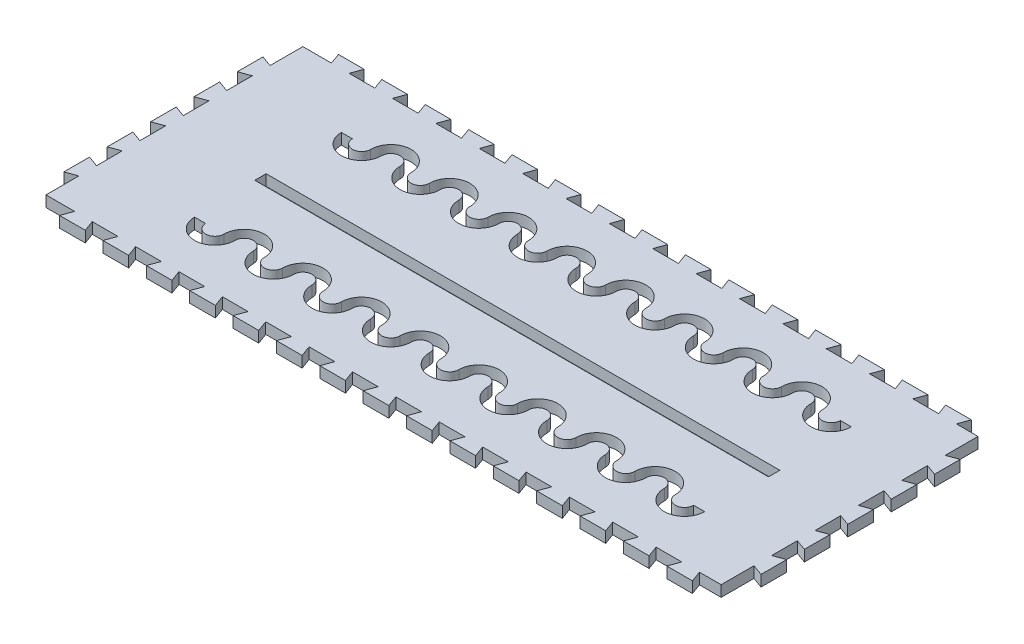
SolidWorks part; units mm, degrees
note: The reader was unsure of these and kept them because the rebuilt part matched: shared geometry of "Sketch1<3>", "Sketch1<4>", "Sketch1<5>".
ref_plane "Front Plane" through (0, 0, 0) normal (0, 0, 1) x (1, 0, 0)
ref_plane "Top Plane" through (0, 0, 0) normal (0, 1, 0) x (1, 0, 0)
ref_plane "Right Plane" through (0, 0, 0) normal (1, 0, 0) x (0, 0, -1)
sketch "Sketch1" plane through (0, 0, 0) normal (0, 1, 0) x (1, 0, 0)
  line L1 (0, 0) -> (184, 0)
  line L2 (0, 0) -> (0, 70)
  line L3 (0, 70) -> (184, 70)
  line L4 (184, 0) -> (184, 70)
  line L5 (165, 31.9) -> (25, 31.9)
  line L6 (165, 31.9) -> (165, 35)
  line L7 (165, 35) -> (25, 35)
  line L8 (25, 31.9) -> (25, 35)
  line L17 (178.0881, 70) -> (179.18, 73)
  line L18 (172.18, 73) -> (173.2719, 70)
  line L19 (178.0881, 70) -> (173.2719, 70)
  line L21 (179.18, 73) -> (172.18, 73)
  line L22 (167.36, 73) -> (160.36, 73)
  line L23 (160.36, 73) -> (161.4519, 70)
  line L24 (166.2681, 70) -> (161.4519, 70)
  line L25 (166.2681, 70) -> (167.36, 73)
  line L26 (155.54, 73) -> (148.54, 73)
  line L27 (148.54, 73) -> (149.6319, 70)
  line L28 (154.4481, 70) -> (149.6319, 70)
  line L29 (154.4481, 70) -> (155.54, 73)
  line L30 (143.72, 73) -> (136.72, 73)
  line L31 (136.72, 73) -> (137.8119, 70)
  line L32 (142.6281, 70) -> (137.8119, 70)
  line L33 (142.6281, 70) -> (143.72, 73)
  line L34 (131.9, 73) -> (124.9, 73)
  line L35 (124.9, 73) -> (125.9919, 70)
  line L36 (130.8081, 70) -> (125.9919, 70)
  line L37 (130.8081, 70) -> (131.9, 73)
  line L38 (120.08, 73) -> (113.08, 73)
  line L39 (113.08, 73) -> (114.1719, 70)
  line L40 (118.9881, 70) -> (114.1719, 70)
  line L41 (118.9881, 70) -> (120.08, 73)
  line L42 (108.26, 73) -> (101.26, 73)
  line L43 (101.26, 73) -> (102.3519, 70)
  line L44 (107.1681, 70) -> (102.3519, 70)
  line L45 (107.1681, 70) -> (108.26, 73)
  line L46 (96.44, 73) -> (89.44, 73)
  line L47 (89.44, 73) -> (90.5319, 70)
  line L48 (95.3481, 70) -> (90.5319, 70)
  line L49 (95.3481, 70) -> (96.44, 73)
  line L50 (84.62, 73) -> (77.62, 73)
  line L51 (77.62, 73) -> (78.7119, 70)
  line L52 (83.5281, 70) -> (78.7119, 70)
  line L53 (83.5281, 70) -> (84.62, 73)
  line L54 (72.8, 73) -> (65.8, 73)
  line L55 (65.8, 73) -> (66.8919, 70)
  line L56 (71.7081, 70) -> (66.8919, 70)
  line L57 (71.7081, 70) -> (72.8, 73)
  line L58 (60.98, 73) -> (53.98, 73)
  line L59 (53.98, 73) -> (55.0719, 70)
  line L60 (59.8881, 70) -> (55.0719, 70)
  line L61 (59.8881, 70) -> (60.98, 73)
  line L62 (49.16, 73) -> (42.16, 73)
  line L63 (42.16, 73) -> (43.2519, 70)
  line L64 (48.0681, 70) -> (43.2519, 70)
  line L65 (48.0681, 70) -> (49.16, 73)
  line L66 (37.34, 73) -> (30.34, 73)
  line L67 (30.34, 73) -> (31.4319, 70)
  line L68 (36.2481, 70) -> (31.4319, 70)
  line L69 (36.2481, 70) -> (37.34, 73)
  line L70 (25.52, 73) -> (18.52, 73)
  line L71 (18.52, 73) -> (19.6119, 70)
  line L72 (24.4281, 70) -> (19.6119, 70)
  line L73 (24.4281, 70) -> (25.52, 73)
  line L74 (13.7, 73) -> (6.7, 73)
  line L75 (6.7, 73) -> (7.7919, 70)
  line L76 (12.6081, 70) -> (7.7919, 70)
  line L77 (12.6081, 70) -> (13.7, 73)
  line L78 (184, 8.95) -> (187, 7.8581)
  line L79 (12.6081, 0) -> (13.7, -3)
  line L80 (12.6081, 0) -> (7.7919, 0)
  line L81 (6.7, -3) -> (7.7919, 0)
  line L82 (13.7, -3) -> (6.7, -3)
  line L83 (24.4281, 0) -> (25.52, -3)
  line L84 (24.4281, 0) -> (19.6119, 0)
  line L85 (18.52, -3) -> (19.6119, 0)
  line L86 (25.52, -3) -> (18.52, -3)
  line L87 (36.2481, 0) -> (37.34, -3)
  line L88 (36.2481, 0) -> (31.4319, 0)
  line L89 (30.34, -3) -> (31.4319, 0)
  line L90 (37.34, -3) -> (30.34, -3)
  line L91 (48.0681, 0) -> (49.16, -3)
  line L92 (48.0681, 0) -> (43.2519, 0)
  line L93 (42.16, -3) -> (43.2519, 0)
  line L94 (49.16, -3) -> (42.16, -3)
  line L95 (59.8881, 0) -> (60.98, -3)
  line L96 (59.8881, 0) -> (55.0719, 0)
  line L97 (53.98, -3) -> (55.0719, 0)
  line L98 (60.98, -3) -> (53.98, -3)
  line L99 (71.7081, 0) -> (72.8, -3)
  line L100 (71.7081, 0) -> (66.8919, 0)
  line L101 (65.8, -3) -> (66.8919, 0)
  line L102 (72.8, -3) -> (65.8, -3)
  line L103 (83.5281, 0) -> (84.62, -3)
  line L104 (83.5281, 0) -> (78.7119, 0)
  line L105 (77.62, -3) -> (78.7119, 0)
  line L106 (84.62, -3) -> (77.62, -3)
  line L107 (95.3481, 0) -> (96.44, -3)
  line L108 (95.3481, 0) -> (90.5319, 0)
  line L109 (89.44, -3) -> (90.5319, 0)
  line L110 (96.44, -3) -> (89.44, -3)
  line L111 (107.1681, 0) -> (108.26, -3)
  line L112 (107.1681, 0) -> (102.3519, 0)
  line L113 (101.26, -3) -> (102.3519, 0)
  line L114 (108.26, -3) -> (101.26, -3)
  line L115 (118.9881, 0) -> (120.08, -3)
  line L116 (118.9881, 0) -> (114.1719, 0)
  line L117 (113.08, -3) -> (114.1719, 0)
  line L118 (120.08, -3) -> (113.08, -3)
  line L119 (130.8081, 0) -> (131.9, -3)
  line L120 (130.8081, 0) -> (125.9919, 0)
  line L121 (124.9, -3) -> (125.9919, 0)
  line L122 (131.9, -3) -> (124.9, -3)
  line L123 (142.6281, 0) -> (143.72, -3)
  line L124 (142.6281, 0) -> (137.8119, 0)
  line L125 (136.72, -3) -> (137.8119, 0)
  line L126 (143.72, -3) -> (136.72, -3)
  line L127 (154.4481, 0) -> (155.54, -3)
  line L128 (154.4481, 0) -> (149.6319, 0)
  line L129 (148.54, -3) -> (149.6319, 0)
  line L130 (155.54, -3) -> (148.54, -3)
  line L131 (166.2681, 0) -> (167.36, -3)
  line L132 (166.2681, 0) -> (161.4519, 0)
  line L133 (160.36, -3) -> (161.4519, 0)
  line L134 (167.36, -3) -> (160.36, -3)
  line L135 (178.0881, 0) -> (179.18, -3)
  line L136 (178.0881, 0) -> (173.2719, 0)
  line L137 (172.18, -3) -> (173.2719, 0)
  line L138 (179.18, -3) -> (172.18, -3)
  line L139 (187, 14.8581) -> (184, 13.7662)
  line L140 (184, 8.95) -> (184, 13.7662)
  line L141 (187, 7.8581) -> (187, 14.8581)
  line L142 (184, 20.771) -> (187, 19.679)
  line L143 (187, 19.679) -> (187, 26.679)
  line L144 (187, 26.679) -> (184, 25.5871)
  line L145 (184, 20.771) -> (184, 25.5871)
  line L146 (184, 32.5919) -> (187, 31.5)
  line L147 (187, 31.5) -> (187, 38.5)
  line L148 (187, 38.5) -> (184, 37.4081)
  line L149 (184, 32.5919) -> (184, 37.4081)
  line L150 (184, 44.4129) -> (187, 43.321)
  line L151 (187, 43.321) -> (187, 50.321)
  line L152 (187, 50.321) -> (184, 49.229)
  line L153 (184, 44.4129) -> (184, 49.229)
  line L154 (184, 56.2338) -> (187, 55.1419)
  line L155 (187, 55.1419) -> (187, 62.1419)
  line L156 (187, 62.1419) -> (184, 61.05)
  line L157 (184, 56.2338) -> (184, 61.05)
  line L158 (0, 61.05) -> (-3, 62.1419)
  line L159 (-3, 62.1419) -> (-3, 55.1419)
  line L160 (-3, 55.1419) -> (0, 56.2338)
  line L161 (0, 61.05) -> (0, 56.2338)
  line L162 (0, 49.23) -> (-3, 50.3219)
  line L163 (-3, 50.3219) -> (-3, 43.3219)
  line L164 (-3, 43.3219) -> (0, 44.4138)
  line L165 (0, 49.23) -> (0, 44.4138)
  line L166 (0, 37.41) -> (-3, 38.5019)
  line L167 (-3, 38.5019) -> (-3, 31.5019)
  line L168 (-3, 31.5019) -> (0, 32.5938)
  line L169 (0, 37.41) -> (0, 32.5938)
  line L170 (0, 25.59) -> (-3, 26.6819)
  line L171 (-3, 26.6819) -> (-3, 19.6819)
  line L172 (-3, 19.6819) -> (0, 20.7738)
  line L173 (0, 25.59) -> (0, 20.7738)
  line L174 (0, 13.77) -> (-3, 14.8619)
  line L175 (-3, 14.8619) -> (-3, 7.8619)
  line L176 (-3, 7.8619) -> (0, 8.9538)
  line L177 (0, 13.77) -> (0, 8.9538)
  arc A0 (59, 55) -> (51, 55) centre (55, 55) ccw
  arc A1 (59, 55) -> (67, 55) centre (63, 55) ccw
  arc A2 (43, 55) -> (35, 55) centre (39, 55) ccw
  arc A3 (43, 55) -> (51, 55) centre (47, 55) ccw
  arc A5 (27, 55) -> (35, 55) centre (31, 55) ccw
  arc A9 (59, 15) -> (51, 15) centre (55, 15) ccw
  arc A11 (59, 15) -> (67, 15) centre (63, 15) ccw
  arc A12 (43, 15) -> (35, 15) centre (39, 15) ccw
  arc A13 (43, 15) -> (51, 15) centre (47, 15) ccw
  arc A15 (27, 15) -> (35, 15) centre (31, 15) ccw
  arc A28 (75, 15) -> (67, 15) centre (71, 15) ccw
  arc A29 (75, 15) -> (83, 15) centre (79, 15) ccw
  arc A30 (91, 15) -> (83, 15) centre (87, 15) ccw
  arc A31 (91, 15) -> (99, 15) centre (95, 15) ccw
  arc A76 (75, 55) -> (67, 55) centre (71, 55) ccw
  arc A77 (75, 55) -> (83, 55) centre (79, 55) ccw
  arc A78 (91, 55) -> (83, 55) centre (87, 55) ccw
  arc A79 (91, 55) -> (99, 55) centre (95, 55) ccw
  arc A126 (107, 15) -> (99, 15) centre (103, 15) ccw
  arc A127 (107, 15) -> (115, 15) centre (111, 15) ccw
  arc A128 (123, 15) -> (115, 15) centre (119, 15) ccw
  arc A129 (123, 15) -> (131, 15) centre (127, 15) ccw
  arc A130 (139, 15) -> (131, 15) centre (135, 15) ccw
  arc A131 (139, 15) -> (147, 15) centre (143, 15) ccw
  arc A132 (155, 15) -> (147, 15) centre (151, 15) ccw
  arc A133 (155, 15) -> (163, 15) centre (159, 15) ccw
  arc A168 (107, 55) -> (99, 55) centre (103, 55) ccw
  arc A169 (107, 55) -> (115, 55) centre (111, 55) ccw
  arc A170 (123, 55) -> (115, 55) centre (119, 55) ccw
  arc A171 (123, 55) -> (131, 55) centre (127, 55) ccw
  arc A172 (139, 55) -> (131, 55) centre (135, 55) ccw
  arc A173 (139, 55) -> (147, 55) centre (143, 55) ccw
  arc A174 (155, 55) -> (147, 55) centre (151, 55) ccw
  arc A175 (155, 55) -> (163, 55) centre (159, 55) ccw
  arc A176 (27, 55) -> (19, 55) centre (23, 55) ccw [skipped]
  arc A178 (27, 15) -> (19, 15) centre (23, 15) ccw [skipped]
  dimension "D1" = 184
  dimension "D2" = 70
  dimension "D3" = 75
  dimension "D4" = 4
  dimension "D5" = 55
  dimension "D6" = 75
  dimension "D7" = 55
  dimension "D9" = 140
  dimension "D10" = 25
  dimension "D11" = 3.1
  dimension "D12" = 70
  dimension "D13" = 70
  dimension "D14" = 3
  dimension "D15" = 7
  dimension "D16" = 4.82
  dimension "D18" = 35
  dimension "D17" = 15
  dimension "D19" = 7
  dimension "D20" = 4.8162
  dimension "D21" = 3
  dimension "D22" = 3
  dimension "D23" = 70
  dimension "D24" = 70
  dimension "D26" = 8.95
  dimension "D27" = 8.95
  dimension "D28" = 7
  dimension "D29" = 4.8162
  dimension "D30" = 3
  dimension "D31" = 3
  dimension "D32" = 70
  dimension "D33" = 70
  dimension "D34" = 8.95
  dimension "D36" = 8.9538
  dimension "D8" = 4
  dimension "D25" = 5
  dimension "D35" = 5
extrude "Boss-Extrude1" add sketch "Sketch1" along normal mid plane 3
extrude "Cut-Extrude-Thin1" cut sketch "Sketch1<3>" against normal mid plane 10 thin
sketch "Sketch1<3>" plane through (0, 0, 0) normal (0, 1, 0) x (1, 0, 0) same geometry as "Sketch1"
extrude "Cut-Extrude-Thin2" cut sketch "Sketch1<4>" against normal mid plane 10 thin contours A15 A12 A13 A9 A11 A28 A29 A30 A31 A126 A127 A128 A129 A130 A131 A132 A133
sketch "Sketch1<4>" plane through (0, 0, 0) normal (0, 1, 0) x (1, 0, 0) same geometry as "Sketch1"
extrude "Cut-Extrude-Thin3" cut sketch "Sketch1<5>" against normal mid plane 10 thin contours A5 A2 A3 A0 A1 A76 A77 A78 A79 A168 A169 A170 A171 A172 A173 A174 A175
sketch "Sketch1<5>" plane through (0, 0, 0) normal (0, 1, 0) x (1, 0, 0) same geometry as "Sketch1"
